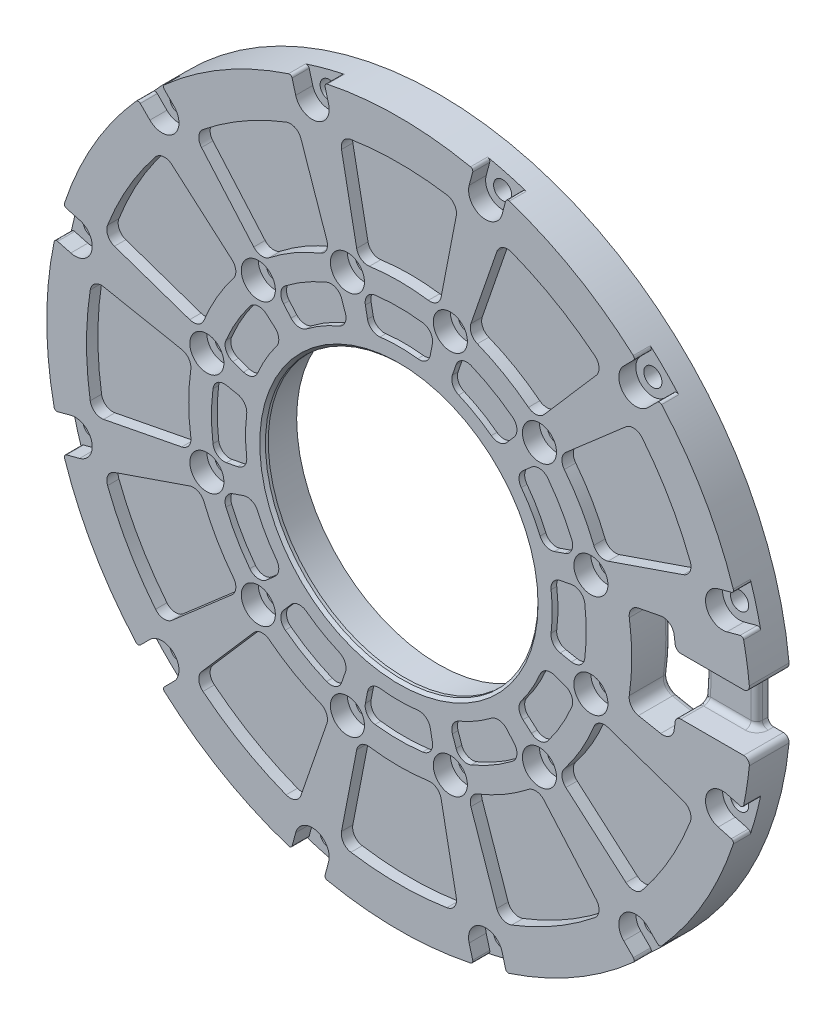
SolidWorks part; units mm, degrees
note: The reader was unsure of these and kept them because the rebuilt part matched: shared geometry of "Sketch12<3>".
material "ABS"
ref_plane "Front Plane" through (0, 0, 0) normal (0, 0, 1) x (1, 0, 0)
ref_plane "Top Plane" through (0, 0, 0) normal (0, 1, 0) x (1, 0, 0)
ref_plane "Right Plane" through (0, 0, 0) normal (1, 0, 0) x (0, 0, -1)
ref_plane "Plane1" through (0, 0, 15) normal (0, 0, 1) x (1, 0, 0)
sketch "Sketch1" plane through (0, 0, 15) normal (0, 0, 1) x (1, 0, 0)
  circle A0 centre (0, 0) radius 39.1
  circle A1 centre (0, 0) radius 32.5 construction
  circle A2 centre (32.5, 0) radius 2.525
  circle A3 centre (28.1458, -16.25) radius 2.525
  circle A4 centre (16.25, -28.1458) radius 2.525
  circle A5 centre (0, -32.5) radius 2.525
  circle A6 centre (-16.25, -28.1458) radius 2.525
  circle A7 centre (-28.1458, -16.25) radius 2.525
  circle A8 centre (-32.5, 0) radius 2.525
  circle A9 centre (-28.1458, 16.25) radius 2.525
  circle A10 centre (-16.25, 28.1458) radius 2.525
  circle A11 centre (0, 32.5) radius 2.525
  circle A12 centre (16.25, 28.1458) radius 2.525
  circle A13 centre (0, 0) radius 16
  circle A14 centre (28.1458, 16.25) radius 2.525
  point P28 (0, 0)
extrude "Boss-Extrude1" add sketch "Sketch1" along normal blind 7
sketch "Sketch2" plane through (0, 0, 15) normal (0, 0, -1) x (-1, 0, 0)
  circle A0 centre (0, 0) radius 25
  dimension "D1" = 50
extrude "Cut-Extrude1" cut sketch "Sketch2" against normal blind 6
sketch "Sketch3" plane through (0, 0, 22) normal (0, 0, 1) x (1, 0, 0)
  circle A1 centre (-16.25, 28.1458) radius 2.55
  circle A2 centre (0, 32.5) radius 2.55
  circle A4 centre (16.25, 28.1458) radius 2.55
  circle A6 centre (28.1458, 16.25) radius 2.55
  circle A8 centre (32.5, 0) radius 2.55
  circle A10 centre (28.1458, -16.25) radius 2.55
  circle A12 centre (16.25, -28.1458) radius 2.55
  circle A14 centre (0, -32.5) radius 2.55
  circle A16 centre (-16.25, -28.1458) radius 2.55
  circle A18 centre (-28.1458, -16.25) radius 2.55
  circle A20 centre (-32.5, 0) radius 2.55
  circle A21 centre (-28.1458, 16.25) radius 2.55
  point P36 (0, 0)
  dimension "D1" = 5.1
  dimension "D3" = 12
extrude "Boss-Extrude2" add sketch "Sketch3" against normal blind 2
chamfer "Chamfer3" distance 0.5 angle 45 12 edges at (35.025, 0, 15) (30.6708, -16.25, 15) (18.775, -28.1458, 15) (2.525, -32.5, 15) (-13.725, -28.1458, 15) (-25.6208, -16.25, 15) (-29.975, 0, 15) (-25.6208, 16.25, 15) (-13.725, 28.1458, 15) (2.525, 32.5, 15) (18.775, 28.1458, 15) (30.6708, 16.25, 15)
sketch "Sketch4" plane through (0, 0, 15) normal (0, 0, -1) x (-1, 0, 0)
  arc A0 (6.049, 32.39) -> (-6.049, 32.39) centre (0, 32.5) ccw
  circle A1 centre (0, 0) radius 39.1
  arc A2 (21.4336, 25.0261) -> (10.9564, 31.0751) centre (16.25, 28.1458) ccw
  arc A3 (31.0751, 10.9564) -> (25.0261, 21.4336) centre (28.1458, 16.25) ccw
  arc A4 (32.39, -6.049) -> (32.39, 6.049) centre (32.5, 0) ccw
  arc A5 (25.0261, -21.4336) -> (31.0751, -10.9564) centre (28.1458, -16.25) ccw
  arc A6 (10.9564, -31.0751) -> (21.4336, -25.0261) centre (16.25, -28.1458) ccw
  arc A7 (-6.049, -32.39) -> (6.049, -32.39) centre (0, -32.5) ccw
  arc A8 (-21.4336, -25.0261) -> (-10.9564, -31.0751) centre (-16.25, -28.1458) ccw
  arc A9 (-31.0751, -10.9564) -> (-25.0261, -21.4336) centre (-28.1458, -16.25) ccw
  arc A10 (-32.39, 6.049) -> (-32.39, -6.049) centre (-32.5, 0) ccw
  arc A11 (-25.0261, 21.4336) -> (-31.0751, 10.9564) centre (-28.1458, 16.25) ccw
  arc A12 (-32.39, -6.049) -> (-31.0751, -10.9564) centre (0, 0) ccw
  arc A13 (-31.0751, 10.9564) -> (-32.39, 6.049) centre (0, 0) ccw
  arc A14 (-6.049, 32.39) -> (-10.9564, 31.0751) centre (0, 0) ccw
  arc A15 (10.9564, 31.0751) -> (6.049, 32.39) centre (0, 0) ccw
  arc A16 (25.0261, 21.4336) -> (21.4336, 25.0261) centre (0, 0) ccw
  arc A17 (32.39, 6.049) -> (31.0751, 10.9564) centre (0, 0) ccw
  arc A18 (31.0751, -10.9564) -> (32.39, -6.049) centre (0, 0) ccw
  arc A19 (21.4336, -25.0261) -> (25.0261, -21.4336) centre (0, 0) ccw
  arc A20 (6.049, -32.39) -> (10.9564, -31.0751) centre (0, 0) ccw
  arc A21 (-10.9564, -31.0751) -> (-6.049, -32.39) centre (0, 0) ccw
  arc A22 (-25.0261, -21.4336) -> (-21.4336, -25.0261) centre (0, 0) ccw
  arc A23 (-10.9564, 31.0751) -> (-21.4336, 25.0261) centre (-16.25, 28.1458) ccw
  arc A24 (-21.4336, 25.0261) -> (-25.0261, 21.4336) centre (0, 0) ccw
  point P28 (0, 0)
  circle M36 centre (0, 0) radius 39.1
  dimension "D1" = 12.1
  dimension "D2" = 78.2
  dimension "D4" = 65.9
  dimension "D3" = 12
extrude "Cut-Extrude2" cut sketch "Sketch4" against normal blind 3 contours A15 A2 A0 M36 | A16 A3 A2 M36 | A17 A4 A3 M36 | A18 A5 A4 M36 | A19 A6 A5 M36 | A20 A7 A6 M36 | A21 A8 A7 M36 | A22 A9 A8 M36 | A12 A10 A9 M36 | A13 A11 A10 M36 | A14 A0 A11 M36
sketch "Sketch5" plane through (0, 0, 22) normal (0, 0, 1) x (1, 0, 0)
  circle A0 centre (0, 0) radius 24
  dimension "D1" = 48
extrude "Cut-Extrude3" cut sketch "Sketch5" against normal through all
chamfer "Chamfer5" distance 0.5 angle 45 1 edges at (24, 0, 22)
sketch "Sketch7" plane through (0, 0, 22) normal (0, 0, 1) x (1, 0, 0)
  line L0 (0, 0) -> (-33.8074, -9.0587) construction
  line L1 (0, 0) -> (-35, 0) construction
  circle A0 centre (-33.8074, -9.0587) radius 1.575
  circle A1 centre (-33.8074, 9.0587) radius 1.575
  circle A2 centre (-24.7487, 24.7487) radius 1.575
  circle A3 centre (-9.0587, 33.8074) radius 1.575
  circle A4 centre (9.0587, 33.8074) radius 1.575
  circle A5 centre (24.7487, 24.7487) radius 1.575
  circle A6 centre (33.8074, 9.0587) radius 1.575
  circle A7 centre (33.8074, -9.0587) radius 1.575
  circle A8 centre (24.7487, -24.7487) radius 1.575
  circle A9 centre (9.0587, -33.8074) radius 1.575
  circle A10 centre (-9.0587, -33.8074) radius 1.575
  circle A11 centre (-24.7487, -24.7487) radius 1.575
  point P26 (0, 0)
  dimension "D2" = 3.15
  dimension "D1" = 35
  dimension "D4" = 15
  dimension "D3" = 12
extrude "Cut-Extrude5" cut sketch "Sketch7" against normal through all
sketch "Sketch8" plane through (0, 0, 22) normal (0, 0, 1) x (1, 0, 0)
  circle A0 centre (0, 0) radius 39.1
  circle A1 centre (0, 0) radius 62
  dimension "D1" = 124
  dimension "D2" = 78.2
  dimension "D3" = 78.2
extrude "Boss-Extrude3" add sketch "Sketch8" against normal blind 7
sketch "Sketch9" plane through (0, 0, 15) normal (0, 0, -1) x (-1, 0, 0)
  circle A0 centre (0, 0) radius 39.1
  circle A1 centre (0, 0) radius 40
  dimension "D1" = 80
  dimension "D2" = 78.2
extrude "Cut-Extrude6" cut sketch "Sketch9" against normal blind 3
sketch "Sketch11" plane through (0, 0, 22) normal (0, 0, 1) x (1, 0, 0)
  line L0 (0, 0) -> (-56.9896, -15.2703) construction
  line L1 (0, 0) -> (-59, 0) construction
  circle A0 centre (-56.9896, -15.2703) radius 1.6
  circle A1 centre (-56.9896, 15.2703) radius 1.6
  circle A2 centre (-41.7193, 41.7193) radius 1.6
  circle A3 centre (-15.2703, 56.9896) radius 1.6
  circle A4 centre (15.2703, 56.9896) radius 1.6
  circle A5 centre (41.7193, 41.7193) radius 1.6
  circle A6 centre (56.9896, 15.2703) radius 1.6
  circle A7 centre (56.9896, -15.2703) radius 1.6
  circle A8 centre (41.7193, -41.7193) radius 1.6
  circle A9 centre (15.2703, -56.9896) radius 1.6
  circle A10 centre (-15.2703, -56.9896) radius 1.6
  circle A11 centre (-41.7193, -41.7193) radius 1.6
  point P27 (0, 0)
  dimension "D2" = 3.2
  dimension "D1" = 59
  dimension "D4" = 15
  dimension "D3" = 12
extrude "Cut-Extrude7" cut sketch "Sketch11" against normal through all
sketch "Sketch12" plane through (0, 0, 22) normal (0, 0, 1) x (1, 0, 0)
  line L0 (0, 0) -> (-56.9896, 15.2703) construction
  line L1 (0, 0) -> (-56.9896, -15.2703) construction
  line L2 (-51.9892, 10.1057) -> (-38.2331, 7.4318)
  line L3 (-51.9892, -10.1057) -> (-38.2331, -7.4318)
  line L4 (-30.367, 5.9028) -> (-28.3994, 5.5203)
  line L5 (-30.367, -5.9028) -> (-28.3994, -5.5203)
  line L6 (-23.3473, 20.2955) -> (-21.8345, 18.9804)
  line L7 (-29.25, 10.0716) -> (-27.3548, 9.419)
  line L8 (-10.0716, 29.25) -> (-9.419, 27.3548)
  line L9 (-20.2955, 23.3473) -> (-18.9804, 21.8345)
  line L10 (5.9028, 30.367) -> (5.5203, 28.3994)
  line L11 (-5.9028, 30.367) -> (-5.5203, 28.3994)
  line L12 (20.2955, 23.3473) -> (18.9804, 21.8345)
  line L13 (10.0716, 29.25) -> (9.419, 27.3548)
  line L14 (29.25, 10.0716) -> (27.3548, 9.419)
  line L15 (23.3473, 20.2955) -> (21.8345, 18.9804)
  line L16 (30.367, -5.9028) -> (28.3994, -5.5203)
  line L17 (30.367, 5.9028) -> (28.3994, 5.5203)
  line L18 (23.3473, -20.2955) -> (21.8345, -18.9804)
  line L19 (29.25, -10.0716) -> (27.3548, -9.419)
  line L20 (10.0716, -29.25) -> (9.419, -27.3548)
  line L21 (20.2955, -23.3473) -> (18.9804, -21.8345)
  line L22 (-5.9028, -30.367) -> (-5.5203, -28.3994)
  line L23 (5.9028, -30.367) -> (5.5203, -28.3994)
  line L24 (-20.2955, -23.3473) -> (-18.9804, -21.8345)
  line L25 (-10.0716, -29.25) -> (-9.419, -27.3548)
  line L26 (-39.9711, 34.7464) -> (-29.3949, 25.5526)
  line L27 (-50.0768, 17.2428) -> (-36.8267, 12.6805)
  line L28 (-17.2428, 50.0768) -> (-12.6805, 36.8267)
  line L29 (-34.7464, 39.9711) -> (-25.5526, 29.3949)
  line L30 (10.1057, 51.9892) -> (7.4318, 38.2331)
  line L31 (-10.1057, 51.9892) -> (-7.4318, 38.2331)
  line L32 (34.7464, 39.9711) -> (25.5526, 29.3949)
  line L33 (17.2428, 50.0768) -> (12.6805, 36.8267)
  line L34 (50.0768, 17.2428) -> (36.8267, 12.6805)
  line L35 (39.9711, 34.7464) -> (29.3949, 25.5526)
  line L36 (51.9892, -10.1057) -> (38.2331, -7.4318) [skipped]
  line L37 (51.9892, 10.1057) -> (38.2331, 7.4318) [skipped]
  line L38 (39.9711, -34.7464) -> (29.3949, -25.5526)
  line L39 (50.0768, -17.2428) -> (36.8267, -12.6805)
  line L40 (17.2428, -50.0768) -> (12.6805, -36.8267)
  line L41 (34.7464, -39.9711) -> (25.5526, -29.3949)
  line L42 (-10.1057, -51.9892) -> (-7.4318, -38.2331)
  line L43 (10.1057, -51.9892) -> (7.4318, -38.2331)
  line L44 (-34.7464, -39.9711) -> (-25.5526, -29.3949)
  line L45 (-17.2428, -50.0768) -> (-12.6805, -36.8267)
  line L46 (-50.0768, -17.2428) -> (-36.8267, -12.6805)
  line L47 (-39.9711, -34.7464) -> (-29.3949, -25.5526)
  line L48 (-29.25, -10.0716) -> (-27.3548, -9.419)
  line L49 (-23.3473, -20.2955) -> (-21.8345, -18.9804)
  arc A0 (-54.3471, 8.4497) -> (-54.3471, -8.4497) centre (0, 0) ccw
  arc A1 (-36.6345, 5.1881) -> (-36.6345, -5.1881) centre (0, 0) ccw
  arc A2 (-51.9892, -10.1057) -> (-54.3471, -8.4497) centre (-52.3708, -8.1424) cw
  arc A3 (-38.2331, -7.4318) -> (-36.6345, -5.1881) centre (-38.6147, -5.4685) ccw
  arc A4 (-38.2331, 7.4318) -> (-36.6345, 5.1881) centre (-38.6147, 5.4685) cw
  arc A5 (-51.9892, 10.1057) -> (-54.3471, 8.4497) centre (-52.3708, 8.1424) ccw
  arc A6 (-32.7324, 4.1937) -> (-32.7324, -4.1937) centre (0, 0) ccw
  arc A7 (-26.7961, 3.3117) -> (-26.7961, -3.3117) centre (0, 0) ccw
  arc A8 (-30.367, -5.9028) -> (-32.7324, -4.1937) centre (-30.7487, -3.9395) cw
  arc A9 (-28.3994, -5.5203) -> (-26.7961, -3.3117) centre (-28.781, -3.557) ccw
  arc A10 (-28.3994, 5.5203) -> (-26.7961, 3.3117) centre (-28.781, 3.557) cw
  arc A11 (-30.367, 5.9028) -> (-32.7324, 4.1937) centre (-30.7487, 3.9395) ccw
  arc A12 (-26.2503, 19.998) -> (-30.444, 12.7344) centre (0, 0) ccw
  arc A13 (-23.3473, 20.2955) -> (-26.2503, 19.998) centre (-24.6594, 18.786) ccw
  arc A14 (-21.8345, 18.9804) -> (-21.5503, 16.2661) centre (-23.1466, 17.471) cw
  arc A15 (-21.5503, 16.2661) -> (-24.862, 10.53) centre (0, 0) ccw
  arc A16 (-27.3548, 9.419) -> (-24.862, 10.53) centre (-26.7036, 11.31) ccw
  arc A17 (-29.25, 10.0716) -> (-30.444, 12.7344) centre (-28.5989, 11.9626) cw
  arc A18 (-12.7344, 30.444) -> (-19.998, 26.2503) centre (0, 0) ccw
  arc A19 (-10.0716, 29.25) -> (-12.7344, 30.444) centre (-11.9626, 28.5989) ccw
  arc A20 (-9.419, 27.3548) -> (-10.53, 24.862) centre (-11.31, 26.7036) cw
  arc A21 (-10.53, 24.862) -> (-16.2661, 21.5503) centre (0, 0) ccw
  arc A22 (-18.9804, 21.8345) -> (-16.2661, 21.5503) centre (-17.471, 23.1466) ccw
  arc A23 (-20.2955, 23.3473) -> (-19.998, 26.2503) centre (-18.786, 24.6594) cw
  arc A24 (4.1937, 32.7324) -> (-4.1937, 32.7324) centre (0, 0) ccw
  arc A25 (5.9028, 30.367) -> (4.1937, 32.7324) centre (3.9395, 30.7487) ccw
  arc A26 (5.5203, 28.3994) -> (3.3117, 26.7961) centre (3.557, 28.781) cw
  arc A27 (3.3117, 26.7961) -> (-3.3117, 26.7961) centre (0, 0) ccw
  arc A28 (-5.5203, 28.3994) -> (-3.3117, 26.7961) centre (-3.557, 28.781) ccw
  arc A29 (-5.9028, 30.367) -> (-4.1937, 32.7324) centre (-3.9395, 30.7487) cw
  arc A30 (19.998, 26.2503) -> (12.7344, 30.444) centre (0, 0) ccw
  arc A31 (20.2955, 23.3473) -> (19.998, 26.2503) centre (18.786, 24.6594) ccw
  arc A32 (18.9804, 21.8345) -> (16.2661, 21.5503) centre (17.471, 23.1466) cw
  arc A33 (16.2661, 21.5503) -> (10.53, 24.862) centre (0, 0) ccw
  arc A34 (9.419, 27.3548) -> (10.53, 24.862) centre (11.31, 26.7036) ccw
  arc A35 (10.0716, 29.25) -> (12.7344, 30.444) centre (11.9626, 28.5989) cw
  arc A36 (30.444, 12.7344) -> (26.2503, 19.998) centre (0, 0) ccw
  arc A37 (29.25, 10.0716) -> (30.444, 12.7344) centre (28.5989, 11.9626) ccw
  arc A38 (27.3548, 9.419) -> (24.862, 10.53) centre (26.7036, 11.31) cw
  arc A39 (24.862, 10.53) -> (21.5503, 16.2661) centre (0, 0) ccw
  arc A40 (21.8345, 18.9804) -> (21.5503, 16.2661) centre (23.1466, 17.471) ccw
  arc A41 (23.3473, 20.2955) -> (26.2503, 19.998) centre (24.6594, 18.786) cw
  arc A42 (32.7324, -4.1937) -> (32.7324, 4.1937) centre (0, 0) ccw
  arc A43 (30.367, -5.9028) -> (32.7324, -4.1937) centre (30.7487, -3.9395) ccw
  arc A44 (28.3994, -5.5203) -> (26.7961, -3.3117) centre (28.781, -3.557) cw
  arc A45 (26.7961, -3.3117) -> (26.7961, 3.3117) centre (0, 0) ccw
  arc A46 (28.3994, 5.5203) -> (26.7961, 3.3117) centre (28.781, 3.557) ccw
  arc A47 (30.367, 5.9028) -> (32.7324, 4.1937) centre (30.7487, 3.9395) cw
  arc A48 (26.2503, -19.998) -> (30.444, -12.7344) centre (0, 0) ccw
  arc A49 (23.3473, -20.2955) -> (26.2503, -19.998) centre (24.6594, -18.786) ccw
  arc A50 (21.8345, -18.9804) -> (21.5503, -16.2661) centre (23.1466, -17.471) cw
  arc A51 (21.5503, -16.2661) -> (24.862, -10.53) centre (0, 0) ccw
  arc A52 (27.3548, -9.419) -> (24.862, -10.53) centre (26.7036, -11.31) ccw
  arc A53 (29.25, -10.0716) -> (30.444, -12.7344) centre (28.5989, -11.9626) cw
  arc A54 (12.7344, -30.444) -> (19.998, -26.2503) centre (0, 0) ccw
  arc A55 (10.0716, -29.25) -> (12.7344, -30.444) centre (11.9626, -28.5989) ccw
  arc A56 (9.419, -27.3548) -> (10.53, -24.862) centre (11.31, -26.7036) cw
  arc A57 (10.53, -24.862) -> (16.2661, -21.5503) centre (0, 0) ccw
  arc A58 (18.9804, -21.8345) -> (16.2661, -21.5503) centre (17.471, -23.1466) ccw
  arc A59 (20.2955, -23.3473) -> (19.998, -26.2503) centre (18.786, -24.6594) cw
  arc A60 (-4.1937, -32.7324) -> (4.1937, -32.7324) centre (0, 0) ccw
  arc A61 (-5.9028, -30.367) -> (-4.1937, -32.7324) centre (-3.9395, -30.7487) ccw
  arc A62 (-5.5203, -28.3994) -> (-3.3117, -26.7961) centre (-3.557, -28.781) cw
  arc A63 (-3.3117, -26.7961) -> (3.3117, -26.7961) centre (0, 0) ccw
  arc A64 (5.5203, -28.3994) -> (3.3117, -26.7961) centre (3.557, -28.781) ccw
  arc A65 (5.9028, -30.367) -> (4.1937, -32.7324) centre (3.9395, -30.7487) cw
  arc A66 (-19.998, -26.2503) -> (-12.7344, -30.444) centre (0, 0) ccw
  arc A67 (-20.2955, -23.3473) -> (-19.998, -26.2503) centre (-18.786, -24.6594) ccw
  arc A68 (-18.9804, -21.8345) -> (-16.2661, -21.5503) centre (-17.471, -23.1466) cw
  arc A69 (-16.2661, -21.5503) -> (-10.53, -24.862) centre (0, 0) ccw
  arc A70 (-9.419, -27.3548) -> (-10.53, -24.862) centre (-11.31, -26.7036) ccw
  arc A71 (-10.0716, -29.25) -> (-12.7344, -30.444) centre (-11.9626, -28.5989) cw
  arc A72 (-39.9711, 34.7464) -> (-42.8411, 34.4912) centre (-41.2832, 33.2369) ccw
  arc A73 (-29.3949, 25.5526) -> (-29.1323, 22.8102) centre (-30.7071, 24.0432) cw
  arc A74 (-36.8267, 12.6805) -> (-34.3204, 13.8242) centre (-36.1756, 14.5715) ccw
  arc A75 (-50.0768, 17.2428) -> (-51.2908, 19.8559) centre (-49.4257, 19.1339) cw
  arc A76 (-42.8411, 34.4912) -> (-51.2908, 19.8559) centre (0, 0) ccw
  arc A77 (-29.1323, 22.8102) -> (-34.3204, 13.8242) centre (0, 0) ccw
  arc A78 (-17.2428, 50.0768) -> (-19.8559, 51.2908) centre (-19.1339, 49.4257) ccw
  arc A79 (-12.6805, 36.8267) -> (-13.8242, 34.3204) centre (-14.5715, 36.1756) cw
  arc A80 (-25.5526, 29.3949) -> (-22.8102, 29.1323) centre (-24.0432, 30.7071) ccw
  arc A81 (-34.7464, 39.9711) -> (-34.4912, 42.8411) centre (-33.2369, 41.2832) cw
  arc A82 (-19.8559, 51.2908) -> (-34.4912, 42.8411) centre (0, 0) ccw
  arc A83 (-13.8242, 34.3204) -> (-22.8102, 29.1323) centre (0, 0) ccw
  arc A84 (10.1057, 51.9892) -> (8.4497, 54.3471) centre (8.1424, 52.3708) ccw
  arc A85 (7.4318, 38.2331) -> (5.1881, 36.6345) centre (5.4685, 38.6147) cw
  arc A86 (-7.4318, 38.2331) -> (-5.1881, 36.6345) centre (-5.4685, 38.6147) ccw
  arc A87 (-10.1057, 51.9892) -> (-8.4497, 54.3471) centre (-8.1424, 52.3708) cw
  arc A88 (8.4497, 54.3471) -> (-8.4497, 54.3471) centre (0, 0) ccw
  arc A89 (5.1881, 36.6345) -> (-5.1881, 36.6345) centre (0, 0) ccw
  arc A90 (34.7464, 39.9711) -> (34.4912, 42.8411) centre (33.2369, 41.2832) ccw
  arc A91 (25.5526, 29.3949) -> (22.8102, 29.1323) centre (24.0432, 30.7071) cw
  arc A92 (12.6805, 36.8267) -> (13.8242, 34.3204) centre (14.5715, 36.1756) ccw
  arc A93 (17.2428, 50.0768) -> (19.8559, 51.2908) centre (19.1339, 49.4257) cw
  arc A94 (34.4912, 42.8411) -> (19.8559, 51.2908) centre (0, 0) ccw
  arc A95 (22.8102, 29.1323) -> (13.8242, 34.3204) centre (0, 0) ccw
  arc A96 (50.0768, 17.2428) -> (51.2908, 19.8559) centre (49.4257, 19.1339) ccw
  arc A97 (36.8267, 12.6805) -> (34.3204, 13.8242) centre (36.1756, 14.5715) cw
  arc A98 (29.3949, 25.5526) -> (29.1323, 22.8102) centre (30.7071, 24.0432) ccw
  arc A99 (39.9711, 34.7464) -> (42.8411, 34.4912) centre (41.2832, 33.2369) cw
  arc A100 (51.2908, 19.8559) -> (42.8411, 34.4912) centre (0, 0) ccw
  arc A101 (34.3204, 13.8242) -> (29.1323, 22.8102) centre (0, 0) ccw
  arc A102 (51.9892, -10.1057) -> (54.3471, -8.4497) centre (52.3708, -8.1424) ccw [skipped]
  arc A103 (38.2331, -7.4318) -> (36.6345, -5.1881) centre (38.6147, -5.4685) cw [skipped]
  arc A104 (38.2331, 7.4318) -> (36.6345, 5.1881) centre (38.6147, 5.4685) ccw [skipped]
  arc A105 (51.9892, 10.1057) -> (54.3471, 8.4497) centre (52.3708, 8.1424) cw [skipped]
  arc A106 (54.3471, -8.4497) -> (54.3471, 8.4497) centre (0, 0) ccw [skipped]
  arc A107 (36.6345, -5.1881) -> (36.6345, 5.1881) centre (0, 0) ccw [skipped]
  arc A108 (39.9711, -34.7464) -> (42.8411, -34.4912) centre (41.2832, -33.2369) ccw
  arc A109 (29.3949, -25.5526) -> (29.1323, -22.8102) centre (30.7071, -24.0432) cw
  arc A110 (36.8267, -12.6805) -> (34.3204, -13.8242) centre (36.1756, -14.5715) ccw
  arc A111 (50.0768, -17.2428) -> (51.2908, -19.8559) centre (49.4257, -19.1339) cw
  arc A112 (42.8411, -34.4912) -> (51.2908, -19.8559) centre (0, 0) ccw
  arc A113 (29.1323, -22.8102) -> (34.3204, -13.8242) centre (0, 0) ccw
  arc A114 (17.2428, -50.0768) -> (19.8559, -51.2908) centre (19.1339, -49.4257) ccw
  arc A115 (12.6805, -36.8267) -> (13.8242, -34.3204) centre (14.5715, -36.1756) cw
  arc A116 (25.5526, -29.3949) -> (22.8102, -29.1323) centre (24.0432, -30.7071) ccw
  arc A117 (34.7464, -39.9711) -> (34.4912, -42.8411) centre (33.2369, -41.2832) cw
  arc A118 (19.8559, -51.2908) -> (34.4912, -42.8411) centre (0, 0) ccw
  arc A119 (13.8242, -34.3204) -> (22.8102, -29.1323) centre (0, 0) ccw
  arc A120 (-10.1057, -51.9892) -> (-8.4497, -54.3471) centre (-8.1424, -52.3708) ccw
  arc A121 (-7.4318, -38.2331) -> (-5.1881, -36.6345) centre (-5.4685, -38.6147) cw
  arc A122 (7.4318, -38.2331) -> (5.1881, -36.6345) centre (5.4685, -38.6147) ccw
  arc A123 (10.1057, -51.9892) -> (8.4497, -54.3471) centre (8.1424, -52.3708) cw
  arc A124 (-8.4497, -54.3471) -> (8.4497, -54.3471) centre (0, 0) ccw
  arc A125 (-5.1881, -36.6345) -> (5.1881, -36.6345) centre (0, 0) ccw
  arc A126 (-34.7464, -39.9711) -> (-34.4912, -42.8411) centre (-33.2369, -41.2832) ccw
  arc A127 (-25.5526, -29.3949) -> (-22.8102, -29.1323) centre (-24.0432, -30.7071) cw
  arc A128 (-12.6805, -36.8267) -> (-13.8242, -34.3204) centre (-14.5715, -36.1756) ccw
  arc A129 (-17.2428, -50.0768) -> (-19.8559, -51.2908) centre (-19.1339, -49.4257) cw
  arc A130 (-34.4912, -42.8411) -> (-19.8559, -51.2908) centre (0, 0) ccw
  arc A131 (-22.8102, -29.1323) -> (-13.8242, -34.3204) centre (0, 0) ccw
  arc A132 (-50.0768, -17.2428) -> (-51.2908, -19.8559) centre (-49.4257, -19.1339) ccw
  arc A133 (-36.8267, -12.6805) -> (-34.3204, -13.8242) centre (-36.1756, -14.5715) cw
  arc A134 (-29.3949, -25.5526) -> (-29.1323, -22.8102) centre (-30.7071, -24.0432) ccw
  arc A135 (-39.9711, -34.7464) -> (-42.8411, -34.4912) centre (-41.2832, -33.2369) cw
  arc A136 (-51.2908, -19.8559) -> (-42.8411, -34.4912) centre (0, 0) ccw
  arc A137 (-34.3204, -13.8242) -> (-29.1323, -22.8102) centre (0, 0) ccw
  arc A138 (-30.444, -12.7344) -> (-26.2503, -19.998) centre (0, 0) ccw
  arc A139 (-29.25, -10.0716) -> (-30.444, -12.7344) centre (-28.5989, -11.9626) ccw
  arc A140 (-27.3548, -9.419) -> (-24.862, -10.53) centre (-26.7036, -11.31) cw
  arc A141 (-24.862, -10.53) -> (-21.5503, -16.2661) centre (0, 0) ccw
  arc A142 (-21.8345, -18.9804) -> (-21.5503, -16.2661) centre (-23.1466, -17.471) ccw
  arc A143 (-23.3473, -20.2955) -> (-26.2503, -19.998) centre (-24.6594, -18.786) cw
  point P152 (0, 0)
  point P274 (0, 0)
  dimension "D1" = 55
  dimension "D2" = 37
  dimension "D5" = 2
  dimension "D6" = 33
  dimension "D7" = 27
  dimension "D8" = 4
  dimension "D10" = 2
  dimension "D3" = 4
  dimension "D4" = 4
  dimension "D9" = 4
  dimension "D11" = 12
  dimension "D12" = 12
extrude "Cut-Extrude9" cut sketch "Sketch12" against normal blind 1 contours A47 L17 A46 A45 A44 L16 A43 A42 | A53 L19 A52 A51 A50 L18 A49 A48 | A59 L21 A58 A57 A56 L20 A55 A54 | A65 L23 A64 A63 A62 L22 A61 A60 | L4 A11 A6 A8 L5 A9 A7 A10 | A71 L25 A70 A69 A68 L24 A67 A66 | A17 L7 A16 A15 A14 L6 A13 A12 | A23 L9 A22 A21 A20 L8 A19 A18 | A29 L11 A28 A27 A26 L10 A25 A24 | A35 L13 A34 A33 A32 L12 A31 A30 | A41 L15 A40 A39 A38 L14 A37 A36 | A143 L49 A142 A141 A140 L48 A139 A138
extrude "Cut-Extrude10" cut sketch "Sketch12<3>" against normal blind 2 contours A113 A109 L38 A108 A112 A111 L39 A110 | A119 A115 L40 A114 A118 A117 L41 A116 | A125 A121 L42 A120 A124 A123 L43 A122 | A131 A127 L44 A126 A130 A129 L45 A128 | L2 A5 A0 A2 L3 A3 A1 A4 | A77 A73 L26 A72 A76 A75 L27 A74 | A83 A79 L28 A78 A82 A81 L29 A80 | A89 A85 L30 A84 A88 A87 L31 A86 | A95 A91 L32 A90 A94 A93 L33 A92 | A101 A97 L34 A96 A100 A99 L35 A98 | A137 A133 L46 A132 A136 A135 L47 A134
sketch "Sketch12<3>" plane through (0, 0, 22) normal (0, 0, 1) x (1, 0, 0) same geometry as "Sketch12"
sketch "Sketch13" plane through (0, 0, 22) normal (0, 0, 1) x (1, 0, 0)
  line L0 (0, 0) -> (56.9896, 15.2703) construction
  line L1 (0, 0) -> (56.9896, -15.2703) construction
  line L2 (46.0947, 8.9599) -> (42.1643, 8.1959)
  line L3 (46.0947, -8.9599) -> (42.1643, -8.1959)
  arc A0 (48.454, 7.2944) -> (48.454, -7.2944) centre (0, 0) cw
  arc A1 (40.567, 5.9428) -> (40.567, -5.9428) centre (0, 0) cw
  arc A2 (42.1643, -8.1959) -> (40.567, -5.9428) centre (42.5459, -6.2327) cw
  arc A3 (46.0947, -8.9599) -> (48.454, -7.2944) centre (46.4763, -6.9966) ccw
  arc A4 (46.0947, 8.9599) -> (48.454, 7.2944) centre (46.4763, 6.9966) cw
  arc A5 (42.1643, 8.1959) -> (40.567, 5.9428) centre (42.5459, 6.2327) ccw
  dimension "D1" = 41
  dimension "D2" = 49
  dimension "D5" = 2
  dimension "D3" = 4
  dimension "D4" = 4
extrude "Cut-Extrude11" cut sketch "Sketch13" against normal through all
sketch "Sketch15" plane through (0, 0, 22) normal (0, 0, 1) x (1, 0, 0)
  line L0 (49, 0) -> (62, 0)
  line L1 (49, 5) -> (48.2052, 5)
  line L2 (49, 0) -> (62, 0)
  line L3 (49, 0) -> (49, -5)
  line L4 (49, -5) -> (62, -5)
  line L5 (62, 0) -> (62, -5)
  line L6 (49, 0) -> (62, 0)
  line L7 (49, 0) -> (49, 5)
  line L8 (49, 5) -> (62, 5)
  line L9 (62, 0) -> (62, 5)
  line L10 (49, -5) -> (48.2052, -5)
  line L11 (48.2052, 5) -> (48.2052, -5)
  arc A0 (48.454, -7.2944) -> (48.454, 7.2944) centre (0, 0) ccw construction
  circle A1 centre (0, 0) radius 62 construction
  dimension "D1" = 5
  dimension "D2" = 5
extrude "Cut-Extrude14" cut sketch "Sketch15" against normal blind 5 contours L0 L9 L8 L7 | L5 L0 L3 L4 | L1 L11 L10 L3 L7
sketch "Sketch16" plane through (0, 0, 22) normal (0, 0, 1) x (1, 0, 0)
  line L0 (49, 5) -> (62, 5) construction
  line L1 (62, -5) -> (58, -5)
  line L2 (62, -5) -> (62, 5)
  line L3 (62, 5) -> (58, 5)
  line L4 (58, -5) -> (58, 5)
  dimension "D1" = 4
extrude "Cut-Extrude15" cut sketch "Sketch16" against normal through all
fillet "Fillet3" radius 1 10 edges at (58, -5, 16) (48.7442, -5, 19.5) (48.7442, 5, 19.5) (58, 5, 16) (53.3721, -5, 17) (49, 0, 17) (53.3721, 5, 17) (58, 0, 17) (61.7981, -5, 18.5) (61.7981, 5, 18.5)
sketch "Sketch17" plane through (0, 0, 22) normal (0, 0, 1) x (1, 0, 0)
  line L0 (-57.7661, -12.3725) -> (-61.6298, -13.4078)
  line L1 (-56.2132, -18.1681) -> (-60.0769, -19.2034)
  line L56 (0, 0) -> (-56.9896, -15.2703)
  line L57 (-61.6298, -13.4078) -> (-60.0769, -19.2034)
  line L58 (-57.7661, 12.3725) -> (-61.6298, 13.4078)
  line L59 (-56.2132, 18.1681) -> (-60.0769, 19.2034)
  line L60 (-60.0769, 19.2034) -> (-61.6298, 13.4078)
  line L61 (-43.8406, 39.598) -> (-46.669, 42.4264)
  line L62 (-39.598, 43.8406) -> (-42.4264, 46.669)
  line L63 (-42.4264, 46.669) -> (-46.669, 42.4264)
  line L64 (-18.1681, 56.2132) -> (-19.2034, 60.0769)
  line L65 (-12.3725, 57.7661) -> (-13.4078, 61.6298)
  line L66 (-13.4078, 61.6298) -> (-19.2034, 60.0769)
  line L67 (12.3725, 57.7661) -> (13.4078, 61.6298)
  line L68 (18.1681, 56.2132) -> (19.2034, 60.0769)
  line L69 (19.2034, 60.0769) -> (13.4078, 61.6298)
  line L70 (39.598, 43.8406) -> (42.4264, 46.669)
  line L71 (43.8406, 39.598) -> (46.669, 42.4264)
  line L72 (46.669, 42.4264) -> (42.4264, 46.669)
  line L73 (56.2132, 18.1681) -> (60.0769, 19.2034)
  line L74 (57.7661, 12.3725) -> (61.6298, 13.4078)
  line L75 (61.6298, 13.4078) -> (60.0769, 19.2034)
  line L76 (57.7661, -12.3725) -> (61.6298, -13.4078)
  line L77 (56.2132, -18.1681) -> (60.0769, -19.2034)
  line L78 (60.0769, -19.2034) -> (61.6298, -13.4078)
  line L79 (43.8406, -39.598) -> (46.669, -42.4264)
  line L80 (39.598, -43.8406) -> (42.4264, -46.669)
  line L81 (42.4264, -46.669) -> (46.669, -42.4264)
  line L82 (18.1681, -56.2132) -> (19.2034, -60.0769)
  line L83 (12.3725, -57.7661) -> (13.4078, -61.6298)
  line L84 (13.4078, -61.6298) -> (19.2034, -60.0769)
  line L85 (-12.3725, -57.7661) -> (-13.4078, -61.6298)
  line L86 (-18.1681, -56.2132) -> (-19.2034, -60.0769)
  line L87 (-19.2034, -60.0769) -> (-13.4078, -61.6298)
  line L88 (-39.598, -43.8406) -> (-42.4264, -46.669)
  line L89 (-43.8406, -39.598) -> (-46.669, -42.4264)
  line L90 (-46.669, -42.4264) -> (-42.4264, -46.669)
  arc A0 (-56.2132, -18.1681) -> (-57.7661, -12.3725) centre (-56.9896, -15.2703) ccw
  arc A11 (-57.7661, 12.3725) -> (-56.2132, 18.1681) centre (-56.9896, 15.2703) ccw
  arc A12 (-43.8406, 39.598) -> (-39.598, 43.8406) centre (-41.7193, 41.7193) ccw
  arc A13 (-18.1681, 56.2132) -> (-12.3725, 57.7661) centre (-15.2703, 56.9896) ccw
  arc A14 (12.3725, 57.7661) -> (18.1681, 56.2132) centre (15.2703, 56.9896) ccw
  arc A15 (39.598, 43.8406) -> (43.8406, 39.598) centre (41.7193, 41.7193) ccw
  arc A16 (56.2132, 18.1681) -> (57.7661, 12.3725) centre (56.9896, 15.2703) ccw
  arc A17 (57.7661, -12.3725) -> (56.2132, -18.1681) centre (56.9896, -15.2703) ccw
  arc A18 (43.8406, -39.598) -> (39.598, -43.8406) centre (41.7193, -41.7193) ccw
  arc A19 (18.1681, -56.2132) -> (12.3725, -57.7661) centre (15.2703, -56.9896) ccw
  arc A20 (-12.3725, -57.7661) -> (-18.1681, -56.2132) centre (-15.2703, -56.9896) ccw
  arc A21 (-39.598, -43.8406) -> (-43.8406, -39.598) centre (-41.7193, -41.7193) ccw
  point P80 (0, 0)
  point P107 (0, 0)
  dimension "D2" = 3
  dimension "D3" = 4
  dimension "D1" = 12
extrude "Cut-Extrude16" cut sketch "Sketch17" against normal blind 3 contours L61 A12 L62 L63 | L70 A15 L71 L72 | L73 A16 L74 L75 | L79 A18 L80 L81 | L88 A21 L89 L90 | L59 L60 L58 A11 | L66 L64 A13 L65 | L69 L67 A14 L68 | L78 L76 A17 L77 | L82 L84 L83 A19 | L87 L85 A20 L86 | L57 L1 A0 L0
sketch "Sketch18" plane through (0, 0, 22) normal (0, 0, 1) x (1, 0, 0)
  circle A0 centre (-33.8074, -9.0587) radius 3
  circle A1 centre (-33.8074, 9.0587) radius 3
  circle A2 centre (-24.7487, 24.7487) radius 3
  circle A3 centre (-9.0587, 33.8074) radius 3
  circle A4 centre (9.0587, 33.8074) radius 3
  circle A5 centre (24.7487, 24.7487) radius 3
  circle A6 centre (33.8074, 9.0587) radius 3
  circle A7 centre (33.8074, -9.0587) radius 3
  circle A8 centre (24.7487, -24.7487) radius 3
  circle A9 centre (9.0587, -33.8074) radius 3
  circle A10 centre (-9.0587, -33.8074) radius 3
  circle A11 centre (-24.7487, -24.7487) radius 3
  point P26 (0, 0)
  dimension "D1" = 6
  dimension "D2" = 12
extrude "Cut-Extrude17" cut sketch "Sketch18" against normal blind 3
fillet "Fillet5" radius 0.5 24 edges at (18.9258, -59.0408, 20.5) (13.1302, -60.5937, 20.5) (-18.9258, -59.0408, 20.5) (-13.1302, -60.5937, 20.5) (-41.6679, -45.9106, 20.5) (-45.9106, -41.6679, 20.5) (-60.5937, 13.1302, 20.5) (-59.0408, 18.9258, 20.5) (-45.9106, 41.6679, 20.5) (-41.6679, 45.9106, 20.5) (-18.9258, 59.0408, 20.5) (-13.1302, 60.5937, 20.5) (18.9258, 59.0408, 20.5) (13.1302, 60.5937, 20.5) (45.9106, 41.6679, 20.5) (41.6679, 45.9106, 20.5) (59.0408, 18.9258, 20.5) (60.5937, 13.1302, 20.5) (59.0408, -18.9258, 20.5) (60.5937, -13.1302, 20.5) (45.9106, -41.6679, 20.5) (41.6679, -45.9106, 20.5) (-59.0408, -18.9258, 20.5) (-60.5937, -13.1302, 20.5)
fillet "Fillet6" radius 1 8 edges at (47.6297, -8.6305, 15) (44.1295, -8.5779, 15) (40.9143, -7.3893, 15) (41, 0, 15) (40.9143, 7.3893, 15) (44.1295, 8.5779, 15) (47.6297, 8.6305, 15) (49, 0, 15)
equation "\"RingPinShaft\"= 5.05"
equation "\"CenterBearingOut\"=32.00"
equation "\"OutputBearingOut\"=50.00"
equation "\"RingPostIn\"=5.15"
equation "\"CamBearingOut\"=15.1"
equation "\"DiskOutputShaft\"=10.1"
equation "\"CenterShaft\"=25.2"
equation "\"Eccentricity\"=2"
equation "\"CycCamShaft\"=10.05"
equation "\"m3Thru\"=3.15"
equation "\"m3Insert\"=4.2"
equation "\"D1@Sketch2\"=\"OutputBearingOut\""
equation "\"D2@Sketch7\"=\"m3Thru\""
equation "\"MountingHoleDiam\"=35"
equation "\"D1@Sketch7\"=\"MountingHoleDiam\""
equation "\"D1@Sketch5\"=\"OutputBearingOut\"-2"
